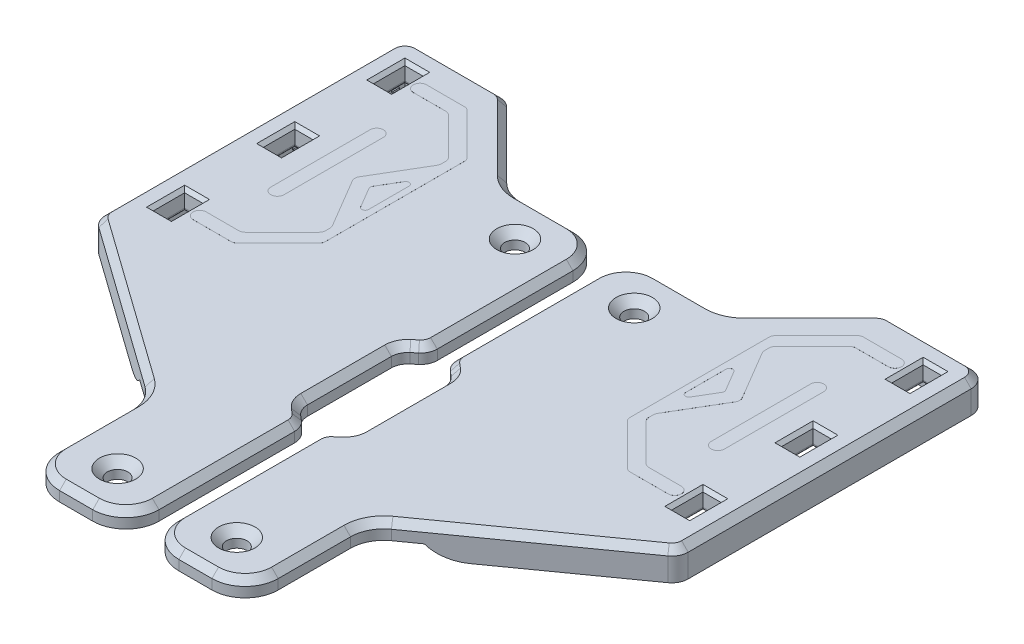
SolidWorks part; units mm, degrees
ref_plane "前视基准面" through (0, 0, 0) normal (0, 0, 1) x (1, 0, 0)
ref_plane "上视基准面" through (0, 0, 0) normal (0, 1, 0) x (1, 0, 0)
ref_plane "右视基准面" through (0, 0, 0) normal (1, 0, 0) x (0, 0, -1)
sketch "草图1" plane through (0, 0, 0) normal (0, 1, 0) x (1, 0, 0)
  line L7 (-15, 72.5) -> (15, 72.5)
  line L9 (-15, -72.5) -> (15, -72.5)
  line L10 (15, 72.5) -> (15, 19.1955)
  line L11 (0, -72.5) -> (0, 72.5) construction
  line L12 (0, 0) -> (15, 0) construction
  line L24 (-65, 91.7535) -> (-65, 11.7535)
  line L33 (-65, 91.7535) -> (-45, 91.7535)
  line L34 (-45, 91.7535) -> (-45, 60.9619)
  line L36 (0, 0) -> (812.2848, 0) construction
  line L37 (15, -19.1955) -> (10, -15)
  line L42 (7, -10) -> (7, 10)
  line L44 (10, -15) -> (10, 15)
  line L45 (10, 15) -> (15, 19.1955)
  line L46 (15, 0) -> (15, -19.1955) construction
  line L47 (15, -19.1955) -> (15, -72.5)
  line L48 (15, 19.1955) -> (15, 0) construction
  line L49 (-10.8357, 69.4917) -> (3.2511, 26.9239) construction
  line L50 (-10.8357, 69.4917) -> (11.9917, 69.4917) construction
  line L51 (11.9917, 69.4917) -> (11.9917, 20.5983) construction
  line L52 (6.9917, 16.4028) -> (11.9917, 20.5983) construction
  line L53 (6.9917, -16.4028) -> (6.9917, 16.4028) construction
  line L54 (11.9917, -20.5983) -> (6.9917, -16.4028) construction
  line L55 (3.2511, 26.9239) -> (-65, 91.7535) construction
  line L56 (-65, 11.7535) -> (-11.1212, 10.8062) construction
  line L58 (-45, 11.7535) -> (-65, 11.7535)
  line L60 (11.9917, -20.5983) -> (11.9917, -69.4917) construction
  line L61 (-11.1212, 10.8062) -> (-11.9601, -69.4917) construction
  line L62 (-11.9601, -69.4917) -> (11.9917, -69.4917) construction
  line L78 (-15, -72.5) -> (-15, -35.4983)
  line L79 (-15, -35.4983) -> (-70, 3.7258)
  line L80 (-3.3729, 37.3649) -> (-68.0083, 98.76) construction
  line L81 (-68.0083, 8.7976) -> (-14.1605, 7.8509) construction
  line L82 (-68.0083, 98.76) -> (-68.0083, 8.7976) construction
  line L83 (-45, 11.7535) -> (-30.5686, 11.7535)
  line L84 (-30.5686, 11.7535) -> (-12.7637, -10)
  line L85 (-12.7637, -10) -> (7, -10)
  line L86 (-70, 3.7258) -> (-70, 96.7535)
  line L87 (-70, 96.7535) -> (-39.2535, 96.7535)
  line L88 (-39.2535, 96.7535) -> (-15, 72.5)
  line L89 (7, 10) -> (-3.2884, 10)
  line L90 (-14.1605, 7.8509) -> (-15, -72.5) construction
  line L91 (-15, 72.5) -> (-3.3729, 37.3649) construction
  line L92 (-3.2884, 10) -> (-45, 60.9619)
  line L94 (-45, 60.9619) -> (-45, 11.7535) construction
  line L95 (-65, 6.3013) -> (-65, 8.7535)
  line L96 (-65, 8.7535) -> (-31.99, 8.7535)
  line L97 (-31.99, 8.7535) -> (-14.185, -13)
  line L98 (-14.185, -13) -> (5, -13)
  line L99 (5, -13) -> (5, -17.3315)
  line L100 (5, -17.3315) -> (10, -21.527)
  line L101 (10, -21.527) -> (10, -47.5)
  line L102 (10, -47.5) -> (-10, -47.5)
  line L103 (-10, -47.5) -> (-10, -32.9229)
  line L104 (-10, -32.9229) -> (-65, 6.3013)
  line L105 (-42, 92.4289) -> (-15, 65.4289)
  line L106 (-15, 65.4289) -> (-15, 55.4788)
  line L107 (-15, 55.4788) -> (-0.2846, 37.5)
  line L108 (-0.2846, 37.5) -> (10, 37.5)
  line L109 (10, 37.5) -> (10, 21.527)
  line L110 (10, 21.527) -> (-0.1621, 13)
  line L111 (-0.1621, 13) -> (-1.8671, 13)
  line L112 (-1.8671, 13) -> (-42, 62.0331)
  line L113 (-42, 62.0331) -> (-42, 92.4289)
  circle A0 centre (0, 60) radius 3.1
  circle A8 centre (0, -60) radius 3.1
  point P4 (0, 0)
  point P24 (7, 0)
  point P43 (10, 0)
  point P56 (-37.7843, 11.7535)
  dimension "D7" = 6.2
  dimension "D11" = 20
  dimension "D12" = 3
  dimension "D13" = 3
  dimension "D14" = 3
  dimension "D15" = 5
  dimension "D16" = 5
  dimension "D2" = 5
  dimension "D3" = 145
  dimension "D4" = 5
  dimension "D5" = 20
  dimension "D6" = 20
  dimension "D8" = 30
  dimension "D9" = 60
  dimension "D10" = 80
  dimension "D17" = 130
  dimension "D18" = 5
  dimension "D19" = 30
  dimension "D20" = 3
  dimension "D21" = 5
  dimension "D22" = 5
  dimension "D23" = 5
  dimension "D24" = 5
  dimension "D25" = 25
  dimension "D26" = 5
  dimension "D27" = 3
  dimension "D28" = 3
  dimension "D29" = 3
  dimension "D30" = 5
  dimension "D31" = 5
  dimension "D32" = 35
  dimension "D33" = 45
  dimension "D34" = 80
  dimension "D35" = 12.5
extrude "凸台-拉伸1" add sketch "草图1" along normal blind 6 contours L88 L87 L86 L79 L78 L9 L47 L37 L44 L45 L10 L7 | A8 | A0
extrude "凸台-拉伸2" add sketch "草图1<3>" against normal blind 3 contours L47 L37 L44 L45 L10 L7 L9 L58 L24 L33 L34 L42 A0 A8 region at (0, 0, -70.606)
sketch "草图1<3>" plane through (0, 0, 0) normal (0, 1, 0) x (1, 0, 0) same geometry as "草图1"
sketch "草图7" plane through (0, 0, 0) normal (0, -1, 0) x (1, 0, 0)
  line L0 (-65, -91.7535) -> (-65, -11.7535) construction
  line L1 (-57.5, -89.7535) -> (-63, -89.7535)
  line L2 (-57.5, -89.7535) -> (-57.5, -80.2535)
  line L3 (-57.5, -80.2535) -> (-63, -80.2535)
  line L4 (-63, -89.7535) -> (-63, -80.2535)
  line L5 (-60.25, -80.2535) -> (-60.25, -89.7535) construction
  line L6 (-57.5, -85.0035) -> (-63, -85.0035) construction
  line L7 (-65, -91.7535) -> (-45, -91.7535) construction
  line L8 (-57.5, -56.5035) -> (-57.5, -47.0035)
  line L9 (-57.5, -56.5035) -> (-63, -56.5035)
  line L10 (-63, -56.5035) -> (-63, -47.0035)
  line L11 (-57.5, -47.0035) -> (-63, -47.0035)
  line L12 (-57.5, -23.2535) -> (-57.5, -13.7535)
  line L13 (-57.5, -23.2535) -> (-63, -23.2535)
  line L14 (-63, -23.2535) -> (-63, -13.7535)
  line L15 (-57.5, -13.7535) -> (-63, -13.7535)
  line L23 (-30.5686, -11.7535) -> (-65, -11.7535) construction
  line L24 (-48.5, -66.7535) -> (-48.5, -36.7535) construction
  line L25 (-50.5, -66.7535) -> (-50.5, -36.7535)
  line L26 (-46.5, -66.7535) -> (-46.5, -36.7535)
  line L27 (-48.5, -51.7535) -> (-57.5, -51.7535) construction
  line L28 (-45, -91.7535) -> (-45, -60.9619) construction
  arc A0 (-50.5, -66.7535) -> (-46.5, -66.7535) centre (-48.5, -66.7535) ccw
  arc A1 (-46.5, -36.7535) -> (-50.5, -36.7535) centre (-48.5, -36.7535) ccw
  point P0 (-60.25, -85.0035)
  point P20 (-48.5, -51.7535)
  dimension "D8" = 2
  dimension "D1" = 5.5
  dimension "D2" = 9.5
  dimension "D3" = 2
  dimension "D4" = 2
  dimension "D6" = 2
  dimension "D7" = 30
  dimension "D9" = 1.5
  dimension "D5" = 3
extrude "切除-拉伸1" cut sketch "草图7" against normal up to next
sketch "草图9" plane through (0, -3, 0) normal (0, -1, 0) x (1, 0, 0)
  line L5 (-45, -91.7535) -> (-45, -60.9619) construction
  line L6 (-65, -91.7535) -> (-45, -91.7535) construction
  line L7 (-65, -91.7535) -> (-65, -11.7535) construction
  line L8 (-65, -11.7535) -> (-30.5686, -11.7535) construction
  line L9 (-45, -91.7535) -> (-45, -60.9619) construction
  line L16 (-65, -91.7535) -> (-45, -91.7535) construction
  line L17 (-65, -91.7535) -> (-65, -11.7535) construction
  line L18 (-65, -11.7535) -> (-30.5686, -11.7535) construction
  line L19 (-45, -60.9619) -> (-45, -11.7535) construction
  line L20 (-45, -11.7535) -> (-65, -11.7535) construction
  line L21 (-44.9, -91.8535) -> (-44.9, -60.9619)
  line L22 (-44.9, -60.9619) -> (-44.9, -11.6535)
  line L23 (-44.9, -11.6535) -> (-65.1, -11.6535)
  line L24 (-65.1, -91.8535) -> (-65.1, -11.6535)
  line L25 (-65.1, -91.8535) -> (-44.9, -91.8535)
  dimension "D1" = 0.1
extrude "切除-拉伸2" cut sketch "草图9" against normal up to surface (3 mm away) up to face at (-60.25, 0, -85.0035)
chamfer "倒角2" distance 1 angle 45 12 edges at (-60.25, 6, -80.2535) (-63, 6, -85.0035) (-60.25, 6, -89.7535) (-57.5, 6, -85.0035) (-63, 6, -51.7535) (-60.25, 6, -56.5035) (-57.5, 6, -51.7535) (-60.25, 6, -47.0035) (-63, 6, -18.5035) (-60.25, 6, -13.7535) (-60.25, 6, -23.2535) (-57.5, 6, -18.5035)
sketch "草图10" plane through (-65.1, 0, 0) normal (1, 0, 0) x (0, 0, -1)
  line L1 (89.8535, -2.15) -> (87.8535, -2.15)
  line L2 (89.8535, -2.15) -> (89.8535, -1.65)
  line L3 (89.8535, -1.65) -> (87.8535, -1.65)
  line L4 (87.8535, -2.15) -> (87.8535, -1.65)
  line L5 (88.8535, -1.65) -> (88.8535, -2.15) construction
  line L6 (89.8535, -1.9) -> (87.8535, -1.9) construction
  line L7 (79.8535, -2.15) -> (79.8535, -1.65)
  line L8 (79.8535, -2.15) -> (77.8535, -2.15)
  line L9 (77.8535, -2.15) -> (77.8535, -1.65)
  line L10 (79.8535, -1.65) -> (77.8535, -1.65)
  line L11 (69.8535, -2.15) -> (69.8535, -1.65)
  line L12 (69.8535, -2.15) -> (67.8535, -2.15)
  line L13 (67.8535, -2.15) -> (67.8535, -1.65)
  line L14 (69.8535, -1.65) -> (67.8535, -1.65)
  line L15 (59.8535, -2.15) -> (59.8535, -1.65)
  line L16 (59.8535, -2.15) -> (57.8535, -2.15)
  line L17 (57.8535, -2.15) -> (57.8535, -1.65)
  line L18 (59.8535, -1.65) -> (57.8535, -1.65)
  line L19 (49.8535, -2.15) -> (49.8535, -1.65)
  line L20 (49.8535, -2.15) -> (47.8535, -2.15)
  line L21 (47.8535, -2.15) -> (47.8535, -1.65)
  line L22 (49.8535, -1.65) -> (47.8535, -1.65)
  line L23 (39.8535, -2.15) -> (39.8535, -1.65)
  line L24 (39.8535, -2.15) -> (37.8535, -2.15)
  line L25 (37.8535, -2.15) -> (37.8535, -1.65)
  line L26 (39.8535, -1.65) -> (37.8535, -1.65)
  line L27 (29.8535, -2.15) -> (29.8535, -1.65)
  line L28 (29.8535, -2.15) -> (27.8535, -2.15)
  line L29 (27.8535, -2.15) -> (27.8535, -1.65)
  line L30 (29.8535, -1.65) -> (27.8535, -1.65)
  line L31 (19.8535, -2.15) -> (19.8535, -1.65)
  line L32 (19.8535, -2.15) -> (17.8535, -2.15)
  line L33 (17.8535, -2.15) -> (17.8535, -1.65)
  line L34 (19.8535, -1.65) -> (17.8535, -1.65)
  line L35 (91.8535, 0) -> (11.6535, 0) construction
  line L36 (91.8535, 0) -> (91.8535, -3) construction
  point P0 (88.8535, -1.9)
  dimension "D1" = 2
  dimension "D2" = 0.5
  dimension "D3" = 1.65
  dimension "D5" = 2
  dimension "D4" = 8
extrude "凸台-拉伸3" add sketch "草图10" along normal blind 0.4
sketch "草图14" plane through (0, 0, 0) normal (0, -1, 0) x (1, 0, 0)
  line L33 (-1.8671, -13) -> (-42, -62.0331) construction
  line L34 (-42, -62.0331) -> (-42, -92.4289) construction
  line L35 (-42, -92.4289) -> (-15, -65.4289) construction
  line L36 (-15, -65.4289) -> (-15, -55.4788) construction
  line L37 (-15, -55.4788) -> (-0.2846, -37.5) construction
  line L38 (-0.2846, -37.5) -> (10, -37.5) construction
  line L39 (10, -37.5) -> (10, -21.527) construction
  line L40 (10, -21.527) -> (-0.1621, -13) construction
  line L41 (-0.1621, -13) -> (-1.8671, -13) construction
  line L42 (-10, 47.5) -> (-10, 32.9229) construction
  line L43 (-10, 32.9229) -> (-65, -6.3013) construction
  line L44 (-65, -6.3013) -> (-65, -8.7535) construction
  line L45 (-65, -8.7535) -> (-31.99, -8.7535) construction
  line L46 (-31.99, -8.7535) -> (-14.185, 13) construction
  line L47 (-14.185, 13) -> (5, 13) construction
  line L48 (5, 13) -> (5, 17.3315) construction
  line L49 (5, 17.3315) -> (10, 21.527) construction
  line L50 (10, 21.527) -> (10, 47.5) construction
  line L51 (10, 47.5) -> (-10, 47.5) construction
  line L52 (-1.8671, -13) -> (-42, -62.0331)
  line L53 (-42, -62.0331) -> (-42, -92.4289)
  line L54 (-42, -92.4289) -> (-15, -65.4289)
  line L55 (-15, -65.4289) -> (-15, -55.4788)
  line L56 (-15, -55.4788) -> (-0.2846, -37.5)
  line L57 (-0.2846, -37.5) -> (10, -37.5)
  line L58 (10, -37.5) -> (10, -21.527)
  line L59 (10, -21.527) -> (-0.1621, -13)
  line L60 (-0.1621, -13) -> (-1.8671, -13)
  line L61 (-10, 47.5) -> (-10, 32.9229)
  line L62 (-10, 32.9229) -> (-65, -6.3013)
  line L63 (-65, -6.3013) -> (-65, -8.7535)
  line L64 (-65, -8.7535) -> (-31.99, -8.7535)
  line L65 (-31.99, -8.7535) -> (-14.185, 13)
  line L66 (-14.185, 13) -> (5, 13)
  line L67 (5, 13) -> (5, 17.3315)
  line L68 (5, 17.3315) -> (10, 21.527)
  line L69 (10, 21.527) -> (10, 47.5)
  line L70 (10, 47.5) -> (-10, 47.5)
  line L84 (-42.5, -57.9074) -> (-42.5, -11.7535)
  line L85 (-3.2884, -10) -> (-44.9, -60.8397) construction
  line L86 (-44.9, -11.7535) -> (-30.5686, -11.7535) construction
  line L87 (-42.5, -11.7535) -> (-30.5686, -11.7535)
  line L88 (-30.5686, -11.7535) -> (-12.7637, 10)
  line L89 (-12.7637, 10) -> (7, 10)
  line L90 (7, 10) -> (7, -10)
  line L91 (7, -10) -> (-3.2884, -10)
  line L92 (-3.2884, -10) -> (-42.5, -57.9074)
  line L93 (-46.5, -66.7535) -> (-46.5, -36.7535) construction
  dimension "D1" = 4
extrude "切除-拉伸4" cut sketch "草图14" against normal blind 3.5
chamfer "倒角4" distance 2 angle 45 1 edges at (-42.5, 0, -34.8304)
sketch "草图15" plane through (0, 6, 0) normal (0, 1, 0) x (1, 0, 0)
  line L0 (-50.5, 66.7535) -> (-50.5, 36.7535) construction
  line L1 (-46.5, 36.7535) -> (-46.5, 66.7535) construction
  line L2 (-50.5, 66.7535) -> (-50.5, 36.7535)
  line L3 (-46.5, 36.7535) -> (-46.5, 66.7535)
  arc A0 (-50.5, 36.7535) -> (-46.5, 36.7535) centre (-48.5, 36.7535) ccw construction
  arc A1 (-46.5, 66.7535) -> (-50.5, 66.7535) centre (-48.5, 66.7535) ccw construction
  arc A2 (-50.5, 36.7535) -> (-46.5, 36.7535) centre (-48.5, 36.7535) ccw
  arc A3 (-46.5, 66.7535) -> (-50.5, 66.7535) centre (-48.5, 66.7535) ccw
extrude "凸台-拉伸6" add sketch "草图15" against normal blind 0.45 separate body
sketch "草图16" plane through (0, 5.55, 0) normal (0, -1, 0) x (-1, 0, 0)
  line L0 (50.5, 36.7535) -> (50.5, 66.7535) construction
  line L1 (46.5, 66.7535) -> (46.5, 36.7535) construction
  line L2 (50.5, 36.7535) -> (50.5, 66.7535)
  line L3 (46.5, 66.7535) -> (46.5, 36.7535)
  arc A0 (50.5, 66.7535) -> (46.5, 66.7535) centre (48.5, 66.7535) ccw construction
  arc A1 (46.5, 36.7535) -> (50.5, 36.7535) centre (48.5, 36.7535) ccw construction
  arc A2 (50.5, 66.7535) -> (46.5, 66.7535) centre (48.5, 66.7535) ccw
  arc A3 (46.5, 36.7535) -> (50.5, 36.7535) centre (48.5, 36.7535) ccw
extrude "凸台-拉伸7" add sketch "草图16" along normal blind 0.45
sketch "草图12" plane through (0, 6, 0) normal (0, 1, 0) x (1, 0, 0)
  line L0 (-29.3994, 15.8679) -> (-29.3994, 28.4181) construction
  line L14 (-46.5, 51.7535) -> (-29.3994, 51.7535) construction
  line L15 (-46.5, 36.7535) -> (-46.5, 66.7535) construction
  line L21 (-56.5, 18.5035) -> (-42.2669, 18.5035) construction
  line L24 (-56.5, 24.2535) -> (-56.5, 12.7535) construction
  line L25 (-42.2669, 18.5035) -> (-29.3994, 31.371) construction
  line L26 (-29.3994, 31.371) -> (-29.3994, 72.1359) construction
  line L27 (-29.3994, 72.1359) -> (-42.2669, 85.0035) construction
  line L28 (-42.2669, 85.0035) -> (-56.5, 85.0035) construction
  line L29 (-54.5719, 16.5035) -> (-41.4385, 16.5035)
  line L30 (-56.5, 90.7535) -> (-56.5, 79.2535) construction
  line L31 (-41.4385, 16.5035) -> (-27.9852, 29.9568)
  line L32 (-54.5719, 20.5035) -> (-43.0953, 20.5035)
  line L33 (-43.0953, 20.5035) -> (-30.8136, 32.7852)
  line L34 (-27.9852, 73.5501) -> (-41.4385, 87.0035)
  line L35 (-41.4385, 87.0035) -> (-54.5719, 87.0035)
  line L36 (-30.8136, 70.7217) -> (-43.0953, 83.0035)
  line L37 (-43.0953, 83.0035) -> (-54.5719, 83.0035)
  line L42 (-27.9852, 29.9568) -> (-27.9852, 37.1731)
  line L43 (-54.5719, 16.5035) -> (-56.5, 18.5035)
  line L44 (-56.5, 18.5035) -> (-54.5719, 20.5035)
  line L45 (-27.9852, 66.3338) -> (-27.9852, 73.5501)
  line L46 (-54.5719, 83.0035) -> (-56.5, 85.0035)
  line L47 (-56.5, 85.0035) -> (-54.5719, 87.0035)
  line L48 (-56.5, 16.5035) -> (-54.5719, 16.5035) construction
  line L49 (-56.5, 16.5035) -> (-41.4385, 16.5035) construction
  line L50 (-56.5, 20.5035) -> (-54.5719, 20.5035) construction
  line L51 (-56.5, 20.5035) -> (-43.0953, 20.5035) construction
  line L52 (-54.5719, 83.0035) -> (-56.5, 83.0035) construction
  line L53 (-43.0953, 83.0035) -> (-56.5, 83.0035) construction
  line L54 (-54.5719, 87.0035) -> (-56.5, 87.0035) construction
  line L55 (-41.4385, 87.0035) -> (-56.5, 87.0035) construction
  line L56 (-43.0953, 20.5035) -> (-43.0953, 83.0035) construction
  line L57 (-54.5719, 16.5035) -> (-54.5719, 87.0035) construction
  line L63 (-35.6428, 51.7535) -> (-29.8652, 41.9816)
  line L64 (-29.8652, 41.9816) -> (-29.8652, 61.5253)
  line L65 (-29.8652, 61.5253) -> (-35.6428, 51.7535)
  line L66 (-30.8136, 32.7852) -> (-30.8136, 35.4936)
  line L67 (-27.9852, 37.1731) -> (-27.9852, 66.3338)
  line L68 (-30.8136, 35.4936) -> (-40.4273, 51.7535)
  line L69 (-40.4273, 51.7535) -> (-30.8136, 68.0133)
  line L70 (-30.8136, 35.4936) -> (-30.8136, 51.7535) construction
  line L71 (-30.8136, 68.0133) -> (-30.8136, 70.7217)
  line L72 (-30.8136, 51.7535) -> (-30.8136, 68.0133) construction
  dimension "D4" = 2
  dimension "D1" = 45
  dimension "D2" = 45
  dimension "D3" = 2
  dimension "D5" = 2
  dimension "D7" = 2
extrude "切除-拉伸3" cut sketch "草图12" against normal blind 0.45
fillet "圆角5" radius 2 17 edges at (-27.9852, 5.775, -73.5501) (-41.4385, 5.775, -87.0035) (-54.5719, 5.775, -87.0035) (-56.5, 5.775, -85.0035) (-54.5719, 5.775, -83.0035) (-43.0953, 5.775, -83.0035) (-27.9852, 5.775, -29.9568) (-41.4385, 5.775, -16.5035) (-43.0953, 5.775, -20.5035) (-54.5719, 5.775, -16.5035) (-54.5719, 5.775, -20.5035) (-56.5, 5.775, -18.5035) (-30.8136, 5.775, -70.7217) (-30.8136, 5.775, -68.0133) (-30.8136, 5.775, -35.4936) (-30.8136, 5.775, -32.7852) (-40.4273, 5.775, -51.7535)
fillet "圆角6" radius 1 3 edges at (-35.6428, 5.775, -51.7535) (-29.8652, 5.775, -61.5253) (-29.8652, 5.775, -41.9816)
ref_plane "基准面2" through (0, 5.56, 0) normal (0, 1, 0) x (1, 0, 0)
sketch "草图13" plane through (0, 5.56, 0) normal (0, 1, 0) x (1, 0, 0)
  line L21 (-31.726, 58.3781) -> (-35.3419, 52.2624)
  line L26 (-31.726, 58.3781) -> (-35.3419, 52.2624)
  line L67 (-35.3419, 51.2445) -> (-31.726, 45.1288)
  line L68 (-35.3419, 51.2445) -> (-31.726, 45.1288)
  line L69 (-29.8652, 45.6378) -> (-29.8652, 57.8691)
  line L70 (-29.8652, 45.6378) -> (-29.8652, 57.8691)
  line L71 (-27.9852, 30.7852) -> (-27.9852, 72.7217)
  line L73 (-28.571, 74.1359) -> (-40.8527, 86.4177)
  line L74 (-42.2669, 87.0035) -> (-53.7219, 87.0035)
  line L75 (-53.7219, 83.0035) -> (-43.9238, 83.0035)
  line L76 (-42.5095, 82.4177) -> (-31.3994, 71.3075)
  line L77 (-30.8136, 69.8933) -> (-30.8136, 68.5603)
  line L78 (-31.092, 67.5424) -> (-39.8255, 52.7714)
  line L79 (-39.8255, 50.7356) -> (-31.092, 35.9645)
  line L80 (-30.8136, 34.9466) -> (-30.8136, 33.6136)
  line L98 (-31.3994, 32.1994) -> (-42.5095, 21.0892)
  line L100 (-43.9238, 20.5035) -> (-53.7219, 20.5035)
  line L102 (-53.7219, 16.5035) -> (-42.2669, 16.5035)
  line L106 (-40.8527, 17.0892) -> (-28.571, 29.371)
  line L108 (-27.9852, 30.7852) -> (-27.9852, 72.7217)
  line L112 (-28.571, 74.1359) -> (-40.8527, 86.4177)
  line L116 (-42.2669, 87.0035) -> (-53.7219, 87.0035)
  line L118 (-53.7219, 83.0035) -> (-43.9238, 83.0035)
  line L120 (-42.5095, 82.4177) -> (-31.3994, 71.3075)
  line L122 (-30.8136, 69.8933) -> (-30.8136, 68.5603)
  line L123 (-31.092, 67.5424) -> (-39.8255, 52.7714)
  line L124 (-39.8255, 50.7356) -> (-31.092, 35.9645)
  line L125 (-30.8136, 34.9466) -> (-30.8136, 33.6136)
  line L126 (-31.3994, 32.1994) -> (-42.5095, 21.0892)
  line L127 (-43.9238, 20.5035) -> (-53.7219, 20.5035)
  line L128 (-53.7219, 16.5035) -> (-42.2669, 16.5035)
  line L129 (-40.8527, 17.0892) -> (-28.571, 29.371)
  arc A18 (-35.3419, 52.2624) -> (-35.3419, 51.2445) centre (-34.4811, 51.7535) ccw
  arc A19 (-35.3419, 52.2624) -> (-35.3419, 51.2445) centre (-34.4811, 51.7535) ccw
  arc A54 (-31.726, 45.1288) -> (-29.8652, 45.6378) centre (-30.8652, 45.6378) ccw
  arc A58 (-31.726, 45.1288) -> (-29.8652, 45.6378) centre (-30.8652, 45.6378) ccw
  arc A59 (-29.8652, 57.8691) -> (-31.726, 58.3781) centre (-30.8652, 57.8691) ccw
  arc A60 (-29.8652, 57.8691) -> (-31.726, 58.3781) centre (-30.8652, 57.8691) ccw
  arc A66 (-27.9852, 72.7217) -> (-28.571, 74.1359) centre (-29.9852, 72.7217) ccw
  arc A67 (-40.8527, 86.4177) -> (-42.2669, 87.0035) centre (-42.2669, 85.0035) ccw
  arc A68 (-53.7219, 87.0035) -> (-55.1618, 86.3916) centre (-53.7219, 85.0035) ccw
  arc A69 (-55.1618, 86.3916) -> (-55.1618, 83.6153) centre (-53.7219, 85.0035) ccw
  arc A70 (-55.1618, 83.6153) -> (-53.7219, 83.0035) centre (-53.7219, 85.0035) ccw
  arc A71 (-42.5095, 82.4177) -> (-43.9238, 83.0035) centre (-43.9238, 81.0035) ccw
  arc A72 (-30.8136, 69.8933) -> (-31.3994, 71.3075) centre (-32.8136, 69.8933) ccw
  arc A73 (-31.092, 67.5424) -> (-30.8136, 68.5603) centre (-32.8136, 68.5603) ccw
  arc A74 (-39.8255, 52.7714) -> (-39.8255, 50.7356) centre (-38.1039, 51.7535) ccw
  arc A75 (-30.8136, 34.9466) -> (-31.092, 35.9645) centre (-32.8136, 34.9466) ccw
  arc A76 (-31.3994, 32.1994) -> (-30.8136, 33.6136) centre (-32.8136, 33.6136) ccw
  arc A77 (-43.9238, 20.5035) -> (-42.5095, 21.0892) centre (-43.9238, 22.5035) ccw
  arc A78 (-53.7219, 20.5035) -> (-55.1618, 19.8916) centre (-53.7219, 18.5035) ccw
  arc A79 (-55.1618, 19.8916) -> (-55.1618, 17.1153) centre (-53.7219, 18.5035) ccw
  arc A80 (-55.1618, 17.1153) -> (-53.7219, 16.5035) centre (-53.7219, 18.5035) ccw
  arc A81 (-42.2669, 16.5035) -> (-40.8527, 17.0892) centre (-42.2669, 18.5035) ccw
  arc A82 (-28.571, 29.371) -> (-27.9852, 30.7852) centre (-29.9852, 30.7852) ccw
  arc A83 (-27.9852, 72.7217) -> (-28.571, 74.1359) centre (-29.9852, 72.7217) ccw
  arc A84 (-40.8527, 86.4177) -> (-42.2669, 87.0035) centre (-42.2669, 85.0035) ccw
  arc A85 (-53.7219, 87.0035) -> (-55.1618, 86.3916) centre (-53.7219, 85.0035) ccw
  arc A86 (-55.1618, 86.3916) -> (-55.1618, 83.6153) centre (-53.7219, 85.0035) ccw
  arc A87 (-55.1618, 83.6153) -> (-53.7219, 83.0035) centre (-53.7219, 85.0035) ccw
  arc A88 (-42.5095, 82.4177) -> (-43.9238, 83.0035) centre (-43.9238, 81.0035) ccw
  arc A89 (-30.8136, 69.8933) -> (-31.3994, 71.3075) centre (-32.8136, 69.8933) ccw
  arc A90 (-31.092, 67.5424) -> (-30.8136, 68.5603) centre (-32.8136, 68.5603) ccw
  arc A91 (-39.8255, 52.7714) -> (-39.8255, 50.7356) centre (-38.1039, 51.7535) ccw
  arc A92 (-30.8136, 34.9466) -> (-31.092, 35.9645) centre (-32.8136, 34.9466) ccw
  arc A93 (-31.3994, 32.1994) -> (-30.8136, 33.6136) centre (-32.8136, 33.6136) ccw
  arc A94 (-43.9238, 20.5035) -> (-42.5095, 21.0892) centre (-43.9238, 22.5035) ccw
  arc A95 (-53.7219, 20.5035) -> (-55.1618, 19.8916) centre (-53.7219, 18.5035) ccw
  arc A96 (-55.1618, 19.8916) -> (-55.1618, 17.1153) centre (-53.7219, 18.5035) ccw
  arc A97 (-55.1618, 17.1153) -> (-53.7219, 16.5035) centre (-53.7219, 18.5035) ccw
  arc A98 (-42.2669, 16.5035) -> (-40.8527, 17.0892) centre (-42.2669, 18.5035) ccw
  arc A99 (-28.571, 29.371) -> (-27.9852, 30.7852) centre (-29.9852, 30.7852) ccw
  dimension "D1" = 0
  dimension "D2" = 0
extrude "凸台-拉伸5" add sketch "草图13" along normal blind 0.45 separate body
fillet "圆角4" radius 1 12 edges at (-60.25, 0, -13.7535) (-57.5, 0, -18.5035) (-60.25, 0, -23.2535) (-63, 0, -18.5035) (-57.5, 0, -51.7535) (-60.25, 0, -47.0035) (-60.25, 0, -56.5035) (-63, 0, -51.7535) (-57.5, 0, -85.0035) (-60.25, 0, -89.7535) (-60.25, 0, -80.2535) (-63, 0, -85.0035)
ref_plane "基准面1" through (18, 0, 0) normal (1, 0, 0) x (0, 0, -1)
hole_wizard "M5 平头机械螺钉的锥形沉头孔1" positions "草图5" profile "草图6" countersink size "M5" standard "ANSI Metric" end condition up to next
sketch "草图5" plane through (0, 6, 0) normal (0, 1, 0) x (1, 0, 0)
  point P0 (0, -60)
  point P15 (0, 60)
sketch "草图6" plane through (0, 6, 60) normal (1, 0, 0) x (0, 0, 1)
  line L0 (0, 0) -> (0, 9)
  line L1 (0, 9) -> (2.9, 9)
  line L2 (2.9, 9) -> (2.9, 2.6)
  line L3 (2.9, 2.6) -> (5.5, 0)
  line L5 (5.5, 0) -> (0, 0)
  line L6 (-2.9, 2.6) -> (-5.5, 0) construction
  line L11 (0, -6.35) -> (0, 107.95) construction
  dimension "通孔孔直径" = 5.8
  dimension "通孔孔深度" = 9
  dimension "近端锥形沉头孔直径" = 11
  dimension "近端锥形沉头孔角度" = 90
sketch "草图17" plane through (0, -3, 0) normal (0, -1, 0) x (1, 0, 0)
  line L0 (15, -92.0907) -> (15, 72.5)
  line L1 (15, 72.5) -> (-25, 72.5)
  line L2 (-25, 72.5) -> (-25, -92.0907)
  line L3 (-25, -92.0907) -> (15, -92.0907)
  line L4 (-15, 72.5) -> (15, 72.5) construction
  line L6 (-15, -65.4289) -> (-15, -55.4788) construction
  line L8 (15, -72.5) -> (15, -19.1955) construction
  dimension "D1" = 10
extrude "切除-拉伸5" cut sketch "草图17" against normal blind 4
fillet "圆角7" radius 10 4 edges at (-25, -3, 25.296) (-25, -3, -2.5816) (-25, -3, -38.8948) (-25, -3, -78.9645)
fillet "圆角8" radius 5 7 edges at (15, 3.5, -19.1955) (15, 3.5, 19.1955) (10, 3.5, 15) (10, 3.5, -15) (-39.2535, 1.5, -96.7535) (-70, 1.5, -96.7535) (-70, 1.5, -3.7258)
fillet "圆角9" radius 10 5 edges at (-15, 3.5, -72.5) (15, 3.5, -72.5) (15, 3.5, 72.5) (-15, 3.5, 72.5) (-15, 3.5, 35.4983)
chamfer "倒角1" distance 2 angle 45 24 edges at (-2.9289, 6, -72.5) (15, 6, -42.0135) (0, 6, 72.5) (10, 6, 0) (12.5, 6, 17.0977) (15, 6, 42.0135) (12.5, 6, -17.0977) (-43.5484, 6, 15.1385) (-15, 6, 51.5746) (14.5315, 6, 19.4139) (-53.1623, 6, -96.7535) (-70, 6, -49.0274) (-27.859, 6, -85.359) (14.5315, 6, -19.4139) (-39.4111, 6, -96.3729) (-68.5355, 6, -95.289) (-69.445, 6, -4.0117) (10.4685, 6, -14.7816) (10.4685, 6, 14.7816) (-14.6847, 6, -73.2612) (12.0711, 6, -69.5711) (-16.11, 6, 36.0701) (-12.0711, 6, 69.5711) (12.0711, 6, 69.5711)
fillet "圆角10" radius 2 24 edges at (-1.8671, 2.25, -13) (-0.1621, 2.25, -13) (10, 2.25, -21.527) (10, 2.25, -37.5) (-0.2846, 2.25, -37.5) (-42, 0.25, -62.0331) (-42, 0.25, -92.4289) (-15, 2.25, -65.4289) (-15, 2.25, -55.4788) (-30.5686, 0.4, -11.7535) (-12.7637, 2.25, 10) (7, 2.25, 10) (-3.2884, 2.25, -10) (7, 2.25, -10) (-31.99, 0.2756, -8.7535) (-65, 0.25, -6.3013) (-65, 0.25, -8.7535) (-10, 2.25, 32.9229) (-10, 2.25, 47.5) (10, 2.25, 47.5) (-14.185, 2.25, 13) (5, 2.25, 13) (5, 2.25, 17.3315) (10, 2.25, 21.527)
mirror "镜向3" about plane through (18, 0, 0) normal (1, 0, 0) of bodies 133 121 143 106 119 118 130
